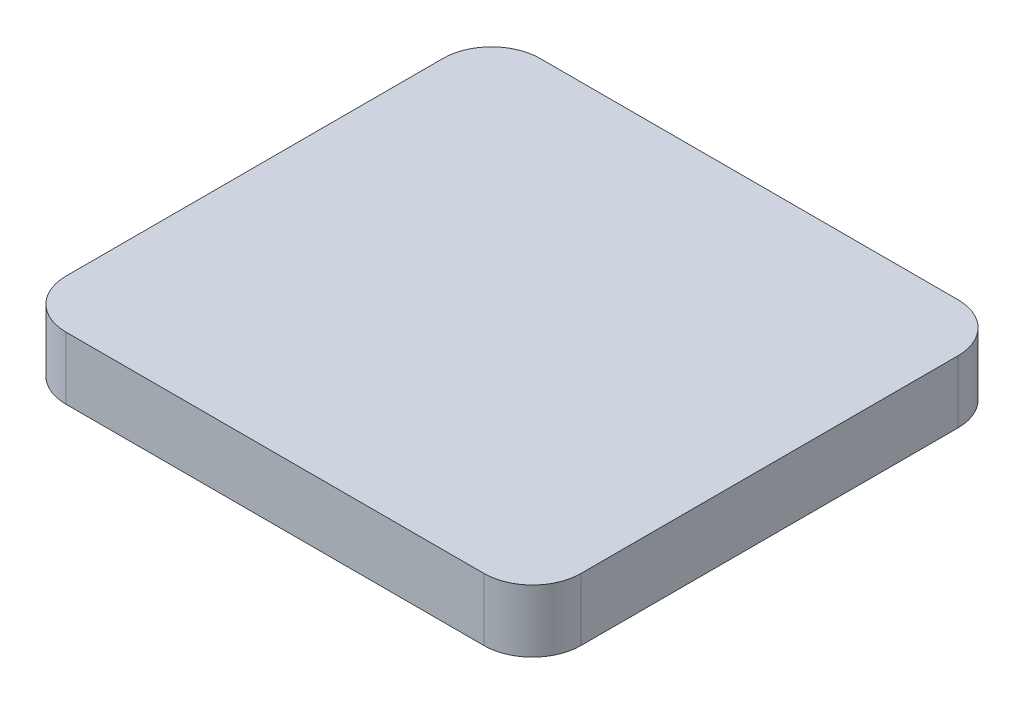
SolidWorks part; units mm, degrees
ref_plane "Front Plane" through (0, 0, 0) normal (0, 0, 1) x (1, 0, 0)
ref_plane "Top Plane" through (0, 0, 0) normal (0, 1, 0) x (1, 0, 0)
ref_plane "Right Plane" through (0, 0, 0) normal (1, 0, 0) x (0, 0, -1)
sketch "Sketch1" plane through (0, 0, 0) normal (0, 1, 0) x (1, 0, 0)
  line L0 (-21.9, 20) -> (-21.9, 22) construction
  line L1 (19.4, 20) -> (-19.4, 20)
  line L2 (21.9, 17.5) -> (21.9, -17.5)
  line L3 (19.4, -20) -> (-19.4, -20)
  line L4 (-21.9, 17.5) -> (-21.9, -17.5)
  line L5 (21.9, 20) -> (-21.9, -20) construction
  line L6 (21.9, -20) -> (-21.9, 20) construction
  line L7 (23.9, -22) -> (-23.9, -22)
  line L8 (23.9, -22) -> (23.9, 22)
  line L9 (23.9, 22) -> (-23.9, 22)
  line L10 (-23.9, -22) -> (-23.9, 22)
  line L11 (23.9, -22) -> (-23.9, 22) construction
  line L12 (23.9, 22) -> (-23.9, -22) construction
  line L13 (-21.9, 20) -> (-23.9, 20) construction
  arc A0 (-19.4, -20) -> (-21.9, -17.5) centre (-19.4, -17.5) cw
  arc A1 (21.9, -17.5) -> (19.4, -20) centre (19.4, -17.5) cw
  arc A2 (19.4, 20) -> (21.9, 17.5) centre (19.4, 17.5) cw
  arc A3 (-19.4, 20) -> (-21.9, 17.5) centre (-19.4, 17.5) ccw
  circle A4 centre (-19.4, 17.5) radius 4.5
  circle A5 centre (19.4, 17.5) radius 4.5
  circle A6 centre (19.4, -17.5) radius 4.5
  circle A7 centre (-19.4, -17.5) radius 4.5
  point P0 (0, 0)
  point P6 (0, 0)
  dimension "D4" = 2.5
  dimension "D1" = 43.8
  dimension "D2" = 40
  dimension "D3" = 2
extrude "Boss-Extrude1" add sketch "Sketch1" along normal blind 1.3 contours L1 A4 L4 A3 | A7 L4 A4 L10 | A7 L3 A0 L4 | A7 L7 A6 L3 | A6 L2 A1 L3 | A6 L8 A5 L2 | L2 A5 L1 A2 | A5 L9 A4 L1 region at (17.5292, 0, -20.1166) region at (0, 0, -21.0286) region at (-17.5292, 0, -20.1166) region at (22.9323, 0, 0) region at (23.2658, 0, 15.4336) region at (-22.9323, 0, 0) region at (0, 0, 21.0286) region at (-22.0166, 0, 15.6292)
sketch "Sketch2" plane through (0, 1.3, 0) normal (0, 1, 0) x (1, 0, 0)
  line L4 (-19.4, -22) -> (19.4, -22)
  line L5 (23.9, -17.5) -> (23.9, 17.5)
  line L6 (19.4, 22) -> (-19.4, 22)
  line L7 (-23.9, 17.5) -> (-23.9, -17.5)
  line L8 (-19.4, -22) -> (19.4, -22)
  line L9 (23.9, -17.5) -> (23.9, 17.5)
  line L10 (19.4, 22) -> (-19.4, 22)
  line L11 (-23.9, 17.5) -> (-23.9, -17.5)
  arc A4 (19.4, -22) -> (23.9, -17.5) centre (19.4, -17.5) ccw
  arc A5 (23.9, 17.5) -> (19.4, 22) centre (19.4, 17.5) ccw
  arc A6 (-19.4, 22) -> (-23.9, 17.5) centre (-19.4, 17.5) ccw
  arc A7 (-23.9, -17.5) -> (-19.4, -22) centre (-19.4, -17.5) ccw
  arc A8 (19.4, -22) -> (23.9, -17.5) centre (19.4, -17.5) ccw
  arc A9 (23.9, 17.5) -> (19.4, 22) centre (19.4, 17.5) ccw
  arc A10 (-19.4, 22) -> (-23.9, 17.5) centre (-19.4, 17.5) ccw
  arc A11 (-23.9, -17.5) -> (-19.4, -22) centre (-19.4, -17.5) ccw
  dimension "D1" = 0
extrude "Boss-Extrude2" add sketch "Sketch2" along normal blind 1.5
sketch "Sketch3" plane through (0, 1.3, 0) normal (0, -1, 0) x (1, 0, 0)
  line L0 (-23.9, 0) -> (23.9, 0) construction
  line L1 (-23.9, 17.5) -> (-23.9, -17.5) construction
  line L2 (23.9, 17.5) -> (23.9, -17.5) construction
  line L3 (-23.9, 11) -> (23.9, 11) construction
  line L4 (0, 11) -> (0, 22) construction
  line L5 (19.4, 22) -> (-19.4, 22) construction
  line L6 (0, 11) -> (0, 0) construction
  line L7 (-23.9, -11) -> (23.9, -11) construction
  line L8 (0, 0) -> (4.1348, 4.1348) construction
  line L9 (11, -23.9) -> (11, 23.9) construction
  line L10 (-11, -23.9) -> (-11, 23.9) construction
  line L11 (-21.9, -17.5) -> (-21.9, 17.5) construction
  line L12 (-21.9, -17.5) -> (-21.9, 17.5) construction
  line L13 (19.4, -20) -> (-19.4, -20) construction
  line L14 (21.9, -17.5) -> (21.9, 17.5) construction
  line L15 (19.4, 20) -> (-19.4, 20) construction
  line L16 (19.4, 20) -> (-19.4, 20) construction
  circle A0 centre (-21.9, 11) radius 0.4
  circle A1 centre (-21.9, 0) radius 0.4
  circle A2 centre (-21.9, -11) radius 0.4
  circle A3 centre (-11, -20) radius 0.4
  circle A4 centre (11, -20) radius 0.4
  circle A5 centre (21.9, -11) radius 0.4
  circle A6 centre (21.9, 0) radius 0.4
  circle A7 centre (21.9, 11) radius 0.4
  circle A8 centre (11, 20) radius 0.4
  circle A9 centre (0, 20) radius 0.4
  circle A10 centre (-11, 20) radius 0.4
  dimension "D2" = 0.8
  dimension "D1" = 45
extrude "Boss-Extrude3" add sketch "Sketch3" along normal up to surface (1.3 mm away) up to face at (0, 0, 0)
sketch "Sketch4" plane through (0, 0, 0) normal (0, -1, 0) x (1, 0, 0)
  line L0 (-22.9, 17.5) -> (-22.9, -17.5)
  line L1 (-19.4, -21) -> (19.4, -21)
  line L2 (22.9, -17.5) -> (22.9, 17.5)
  line L3 (19.4, 21) -> (-19.4, 21)
  line L4 (19.4, 22) -> (-19.4, 22)
  line L5 (-23.9, 17.5) -> (-23.9, -17.5)
  line L6 (-19.4, -22) -> (19.4, -22)
  line L7 (23.9, -17.5) -> (23.9, 17.5)
  line L8 (19.4, 22) -> (-19.4, 22)
  line L9 (-23.9, 17.5) -> (-23.9, -17.5)
  line L10 (-19.4, -22) -> (19.4, -22)
  line L11 (23.9, -17.5) -> (23.9, 17.5)
  arc A0 (-19.4, 21) -> (-22.9, 17.5) centre (-19.4, 17.5) ccw
  arc A1 (-22.9, -17.5) -> (-19.4, -21) centre (-19.4, -17.5) ccw
  arc A2 (19.4, -21) -> (22.9, -17.5) centre (19.4, -17.5) ccw
  arc A3 (22.9, 17.5) -> (19.4, 21) centre (19.4, 17.5) ccw
  arc A4 (-19.4, 22) -> (-23.9, 17.5) centre (-19.4, 17.5) ccw
  arc A5 (-23.9, -17.5) -> (-19.4, -22) centre (-19.4, -17.5) ccw
  arc A6 (19.4, -22) -> (23.9, -17.5) centre (19.4, -17.5) ccw
  arc A7 (23.9, 17.5) -> (19.4, 22) centre (19.4, 17.5) ccw
  arc A8 (-19.4, 22) -> (-23.9, 17.5) centre (-19.4, 17.5) ccw
  arc A9 (-23.9, -17.5) -> (-19.4, -22) centre (-19.4, -17.5) ccw
  arc A10 (19.4, -22) -> (23.9, -17.5) centre (19.4, -17.5) ccw
  arc A11 (23.9, 17.5) -> (19.4, 22) centre (19.4, 17.5) ccw
  dimension "D1" = 0
  dimension "D2" = 1
extrude "Boss-Extrude4" add sketch "Sketch4" along normal blind 3
sketch "Sketch5" plane through (0, 1.3, 0) normal (0, -1, 0) x (1, 0, 0)
  line L31 (-11.9798, 19) -> (-19.4, 19)
  line L32 (-20.9, 17.5) -> (-20.9, 11.9798)
  line L33 (-20.9, 10.0202) -> (-20.9, 0.9798)
  line L34 (-20.9, -0.9798) -> (-20.9, -10.0202)
  line L35 (-20.9, -11.9798) -> (-20.9, -17.5)
  line L36 (-19.4, -19) -> (-11.9798, -19)
  line L37 (-10.0202, -19) -> (10.0202, -19)
  line L38 (11.9798, -19) -> (19.4, -19)
  line L39 (20.9, -17.5) -> (20.9, -11.9798)
  line L40 (20.9, -10.0202) -> (20.9, -0.9798)
  line L41 (20.9, 0.9798) -> (20.9, 10.0202)
  line L42 (20.9, 11.9798) -> (20.9, 17.5)
  line L43 (19.4, 19) -> (11.9798, 19)
  line L44 (10.0202, 19) -> (0.9798, 19)
  line L45 (-0.9798, 19) -> (-10.0202, 19)
  line L46 (-11.9798, 19) -> (-19.4, 19)
  line L47 (-20.9, 17.5) -> (-20.9, 11.9798)
  line L48 (-20.9, 10.0202) -> (-20.9, 0.9798)
  line L49 (-20.9, -0.9798) -> (-20.9, -10.0202)
  line L50 (-20.9, -11.9798) -> (-20.9, -17.5)
  line L51 (-19.4, -19) -> (-11.9798, -19)
  line L52 (-10.0202, -19) -> (10.0202, -19)
  line L53 (11.9798, -19) -> (19.4, -19)
  line L54 (20.9, -17.5) -> (20.9, -11.9798)
  line L55 (20.9, -10.0202) -> (20.9, -0.9798)
  line L56 (20.9, 0.9798) -> (20.9, 10.0202)
  line L57 (20.9, 11.9798) -> (20.9, 17.5)
  line L58 (19.4, 19) -> (11.9798, 19)
  line L59 (10.0202, 19) -> (0.9798, 19)
  line L60 (-0.9798, 19) -> (-10.0202, 19)
  arc A30 (-11.9798, 19) -> (-10.0202, 19) centre (-11, 20) ccw
  arc A31 (-19.4, 19) -> (-20.9, 17.5) centre (-19.4, 17.5) ccw
  arc A32 (-20.9, 10.0202) -> (-20.9, 11.9798) centre (-21.9, 11) ccw
  arc A33 (-20.9, -0.9798) -> (-20.9, 0.9798) centre (-21.9, 0) ccw
  arc A34 (-20.9, -11.9798) -> (-20.9, -10.0202) centre (-21.9, -11) ccw
  arc A35 (-20.9, -17.5) -> (-19.4, -19) centre (-19.4, -17.5) ccw
  arc A36 (-10.0202, -19) -> (-11.9798, -19) centre (-11, -20) ccw
  arc A37 (11.9798, -19) -> (10.0202, -19) centre (11, -20) ccw
  arc A38 (19.4, -19) -> (20.9, -17.5) centre (19.4, -17.5) ccw
  arc A39 (20.9, -10.0202) -> (20.9, -11.9798) centre (21.9, -11) ccw
  arc A40 (20.9, 0.9798) -> (20.9, -0.9798) centre (21.9, 0) ccw
  arc A41 (20.9, 11.9798) -> (20.9, 10.0202) centre (21.9, 11) ccw
  arc A42 (20.9, 17.5) -> (19.4, 19) centre (19.4, 17.5) ccw
  arc A43 (10.0202, 19) -> (11.9798, 19) centre (11, 20) ccw
  arc A44 (-0.9798, 19) -> (0.9798, 19) centre (0, 20) ccw
  arc A45 (-11.9798, 19) -> (-10.0202, 19) centre (-11, 20) ccw
  arc A46 (-19.4, 19) -> (-20.9, 17.5) centre (-19.4, 17.5) ccw
  arc A47 (-20.9, 10.0202) -> (-20.9, 11.9798) centre (-21.9, 11) ccw
  arc A48 (-20.9, -0.9798) -> (-20.9, 0.9798) centre (-21.9, 0) ccw
  arc A49 (-20.9, -11.9798) -> (-20.9, -10.0202) centre (-21.9, -11) ccw
  arc A50 (-20.9, -17.5) -> (-19.4, -19) centre (-19.4, -17.5) ccw
  arc A51 (-10.0202, -19) -> (-11.9798, -19) centre (-11, -20) ccw
  arc A52 (11.9798, -19) -> (10.0202, -19) centre (11, -20) ccw
  arc A53 (19.4, -19) -> (20.9, -17.5) centre (19.4, -17.5) ccw
  arc A54 (20.9, -10.0202) -> (20.9, -11.9798) centre (21.9, -11) ccw
  arc A55 (20.9, 0.9798) -> (20.9, -0.9798) centre (21.9, 0) ccw
  arc A56 (20.9, 11.9798) -> (20.9, 10.0202) centre (21.9, 11) ccw
  arc A57 (20.9, 17.5) -> (19.4, 19) centre (19.4, 17.5) ccw
  arc A58 (10.0202, 19) -> (11.9798, 19) centre (11, 20) ccw
  arc A59 (-0.9798, 19) -> (0.9798, 19) centre (0, 20) ccw
  dimension "D1" = 1
extrude "Cut-Extrude1" cut sketch "Sketch5" against normal blind 0.5
